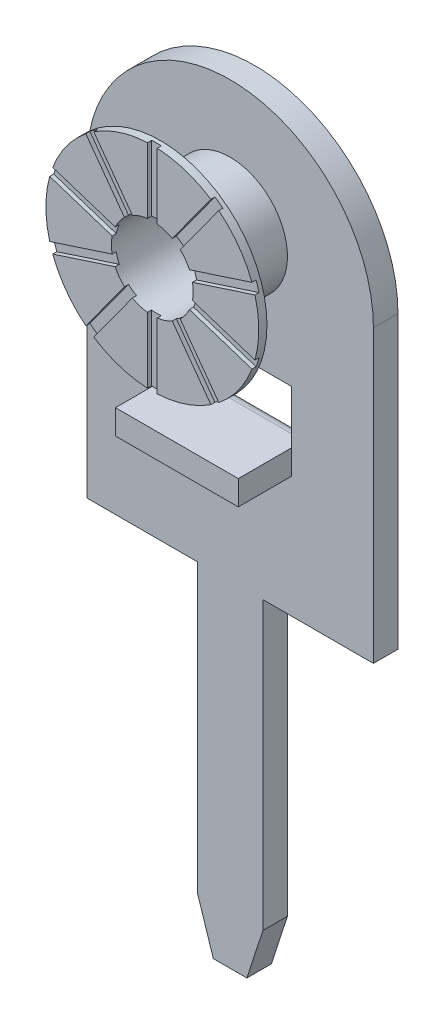
SolidWorks part; units mm, degrees
ref_plane "Front Plane" through (0, 0, 0) normal (0, 0, 1) x (1, 0, 0)
ref_plane "Top Plane" through (0, 0, 0) normal (0, 1, 0) x (1, 0, 0)
ref_plane "Right Plane" through (0, 0, 0) normal (1, 0, 0) x (0, 0, -1)
sketch "Sketch1" plane through (0, 0, 0) normal (0, 0, 1) x (1, 0, 0)
  line L0 (-2.15, -5.3) -> (-3.5, -5.3)
  line L1 (0, 0) -> (-3.5, 0)
  line L2 (0, 0) -> (0, -5.3)
  line L3 (0, -5.3) -> (-1.35, -5.3)
  line L4 (-3.5, 0) -> (-3.5, -5.3)
  line L6 (-2.15, -5.3) -> (-2.15, -9.4)
  line L7 (-2.15, -9.4) -> (-1.35, -9.4)
  line L8 (-1.35, -5.3) -> (-1.35, -9.4)
  line L9 (-2.5, -2.87) -> (-1, -2.87)
  line L10 (-2.5, -2.87) -> (-2.5, -3.67)
  line L11 (-2.5, -3.67) -> (-1, -3.67)
  line L12 (-1, -2.87) -> (-1, -3.67)
  circle A0 centre (-1.75, -1.52) radius 0.5
  point P10 (-1.75, -9.4)
  point P17 (-1.75, -3.67)
  point P18 (-1.75, 0)
  dimension "D5" = 1.63
  dimension "D8" = 1
  dimension "D1" = 3.5
  dimension "D2" = 5.3
  dimension "D3" = 4.1
  dimension "D4" = 0.8
  dimension "D6" = 1.5
  dimension "D7" = 0.8
  dimension "D9" = 2.15
extrude "Boss-Extrude1" add sketch "Sketch1" along normal mid plane 0.3
fillet "Fillet1" 2 edges at (0, 0, 0) (-3.5, 0, 0) type full round first side face at (0, -2.65, 0) second side face at (-3.5, -2.65, 0) middle face at (-1.75, 0, 0)
chamfer "Chamfer1" distance 0.6 angle 18 2 edges at (-1.35, -9.4, 0) (-2.15, -9.4, 0) first distance on face at (-1.35, -7.35, 0) first distance on face at (-2.15, -7.35, 0)
sketch "Sketch2" plane through (0, 0, 0) normal (0, 0, 1) x (1, 0, 0)
  line L0 (-2.5, -2.87) -> (-2.5, -3.67) construction
  line L1 (-2.5, -3.52) -> (-1, -3.52)
  line L2 (-2.5, -3.52) -> (-2.5, -3.82)
  line L3 (-2.5, -3.82) -> (-1, -3.82)
  line L4 (-1, -3.52) -> (-1, -3.82)
  point P6 (-1, -3.67)
  dimension "D1" = 0.3
extrude "Boss-Extrude2" add sketch "Sketch2" along normal blind 0.8
sketch "Sketch3" plane through (0, 0, 0) normal (1, 0, 0) x (0, 0, -1)
  line L0 (0.15, -3.67) -> (0, -3.67)
  line L1 (0, -3.67) -> (0, -3.52)
  line L4 (0, -3.67) -> (0, -3.52) construction
  line L5 (0, -3.67) -> (0.15, -3.67) construction
  arc A0 (0, -3.52) -> (0.15, -3.67) centre (0, -3.67) cw
extrude "Boss-Extrude3" add sketch "Sketch3" against normal up to surface (2.5 mm away) from surface up to face at (-2.5, -3.3533, 0) starting at face at (-1, -3.3533, 0)
sketch "Sketch4" plane through (0, 0, 0) normal (0, 0, 1) x (1, 0, 0)
  circle A0 centre (-1.75, -1.52) radius 0.7
  circle A1 centre (-1.75, -1.52) radius 0.5 construction
  circle A2 centre (-1.75, -1.52) radius 0.5
  dimension "D1" = 0.2
extrude "Boss-Extrude4" add sketch "Sketch4" along normal blind 1
sketch "Sketch5" plane through (0, 0, 0) normal (0, 0, 1) x (1, 0, 0)
  circle A0 centre (-1.75, -1.52) radius 0.5
  circle A1 centre (-1.75, -1.52) radius 1.3
  circle A2 centre (-1.75, -1.52) radius 0.5 construction
  dimension "D1" = 0.8
extrude "Boss-Extrude5" add sketch "Sketch5" along normal blind 0.1 from surface starting at face at (-1.05, -1.52, 1)
sketch "Sketch6" plane through (0, 0, 0) normal (0, 0, 1) x (1, 0, 0)
  line L0 (-0.4951, -1.1753) -> (-2.9678, -1.9788)
  line L1 (-1.81, -0.22) -> (-1.69, -0.22)
  line L2 (-1.81, -0.22) -> (-1.81, -2.82)
  line L3 (-1.81, -2.82) -> (-1.69, -2.82)
  line L4 (-1.69, -0.22) -> (-1.69, -2.82)
  line L5 (-1.81, -0.22) -> (-1.69, -2.82) construction
  line L6 (-1.81, -2.82) -> (-1.69, -0.22) construction
  line L7 (-0.5322, -1.0612) -> (-3.0049, -1.8647)
  line L8 (-0.5322, -1.0612) -> (-0.4951, -1.1753)
  line L9 (-3.0049, -1.8647) -> (-2.9678, -1.9788)
  line L10 (-1.0344, -2.607) -> (-2.5627, -0.5035)
  line L11 (-0.9373, -2.5365) -> (-2.4656, -0.433)
  line L12 (-0.9373, -2.5365) -> (-1.0344, -2.607)
  line L13 (-2.4656, -0.433) -> (-2.5627, -0.5035)
  line L14 (-2.5627, -2.5365) -> (-1.0344, -0.433)
  line L15 (-2.4656, -2.607) -> (-0.9373, -0.5035)
  line L16 (-2.4656, -2.607) -> (-2.5627, -2.5365)
  line L17 (-0.9373, -0.5035) -> (-1.0344, -0.433)
  line L18 (-2.9678, -1.0612) -> (-0.4951, -1.8647)
  line L19 (-3.0049, -1.1753) -> (-0.5322, -1.9788)
  line L20 (-3.0049, -1.1753) -> (-2.9678, -1.0612)
  line L21 (-0.5322, -1.9788) -> (-0.4951, -1.8647)
  point P0 (-1.75, -1.52)
  point P24 (-1.75, -1.52)
  dimension "D1" = 0.12
  dimension "D2" = 2.6
  dimension "D3" = 5
extrude "Cut-Extrude1" cut sketch "Sketch6" against normal blind 0.05 from surface contours L11 L14 L4 L1 L2 | L10 L18 L2 L11 L13 | L20 L19 L7 L10 L18 | L19 L7 L9 L0 L14 | L15 L17 L14 L4 L7 | L15 L18 L0 L8 L7 | L19 L21 L18 L0 L11 | L16 L15 L2 L0 L14 | L19 L4 L10 L12 L11 | L15 L2 L3 L4 L10 region at (-1.0639, -1.2971, 0) region at (-1.0639, -1.7429, 0) region at (-1.3259, -0.9363, 0) region at (-1.3259, -2.1037, 0) region at (-1.75, -0.7986, 0) region at (-1.75, -2.2414, 0) region at (-2.1741, -0.9363, 0) region at (-2.1741, -2.1037, 0) region at (-2.4361, -1.7429, 0) region at (-2.4361, -1.2971, 0) starting at face at (-0.45, -1.52, 1.1)
